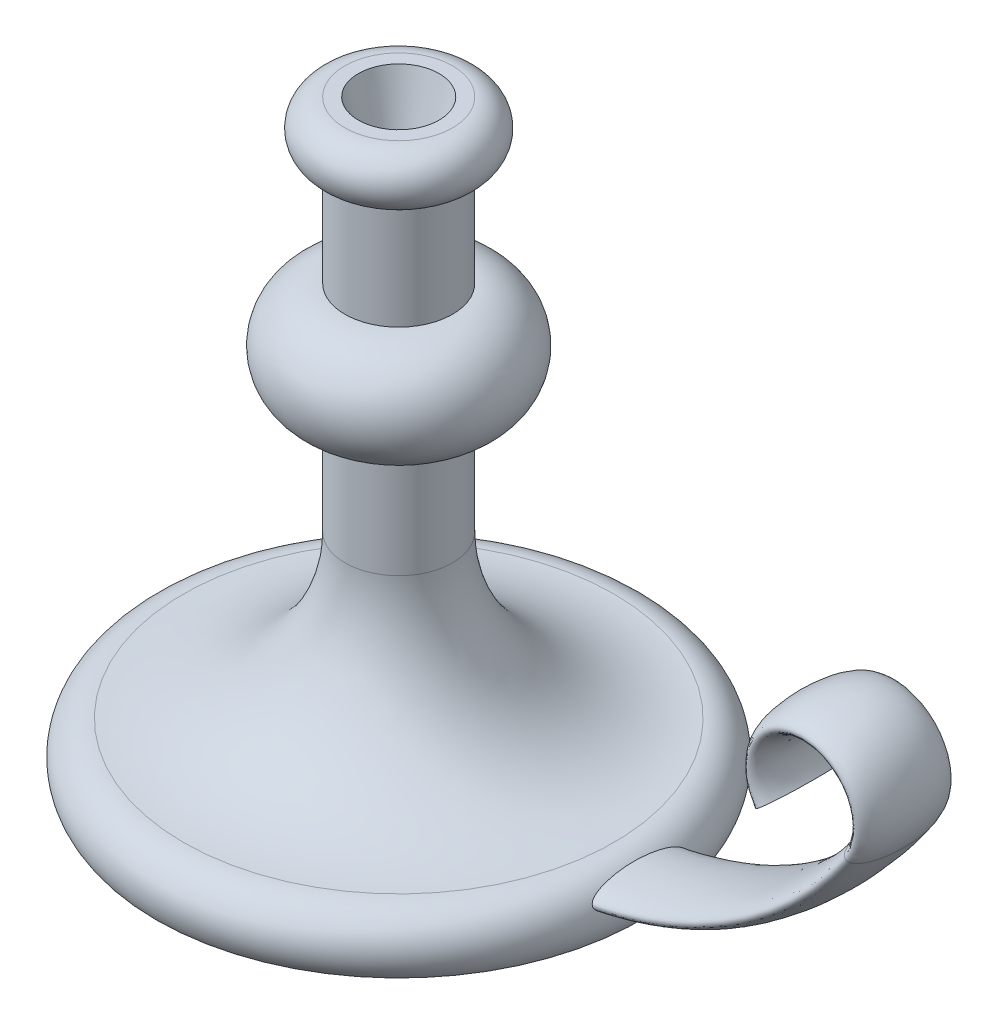
SolidWorks part; units mm, degrees
ref_plane "Front Plane" through (0, 0, 0) normal (0, 0, 1) x (1, 0, 0)
ref_plane "Top Plane" through (0, 0, 0) normal (0, 1, 0) x (1, 0, 0)
ref_plane "Right Plane" through (0, 0, 0) normal (1, 0, 0) x (0, 0, -1)
sketch "Sketch1" plane through (0, 0, 0) normal (0, 0, 1) x (1, 0, 0)
  line L0 (0, 0) -> (0, 220)
  line L1 (0, 220) -> (20, 220)
  line L2 (20, 200) -> (20, 160)
  line L3 (20, 120) -> (20, 80)
  line L4 (90, 0) -> (0, 0)
  arc A0 (20, 220) -> (20, 200) centre (20, 210) cw
  arc A1 (20, 160) -> (20, 120) centre (20, 140) cw
  arc A2 (20, 80) -> (80, 20) centre (80, 80) ccw
  arc A3 (80, 20) -> (90, 0) centre (80, 7.5) cw
  dimension "D3" = 10
  dimension "D5" = 20
  dimension "D6" = 60
  dimension "D7" = 12.5
  dimension "D1" = 220
  dimension "D2" = 20
  dimension "D4" = 40
  dimension "D8" = 80
  dimension "D9" = 90
revolve "Revolve1" add sketch "Sketch1" angle 360 about L0
sketch "Sketch2" plane through (0, 0, 0) normal (0, 0, 1) x (1, 0, 0)
  line L0 (0, 10) -> (60, 10)
  line L1 (-90, 0) -> (90, 0) construction
  arc A0 (60, 10) -> (183.5921, 75) centre (60, 160) ccw
  arc A1 (183.5921, 75) -> (150.6342, 75) centre (167.1131, 86.3333) ccw
  point P6 (0, 0)
  point P11 (60, 160)
  point P12 (150.4294, 75)
  point P13 (0, 0)
  dimension "D3" = 150
  dimension "D5" = 20
  dimension "D1" = 60
  dimension "D2" = 10
  dimension "D4" = 65
sketch "Sketch3" plane through (0, 0, 0) normal (1, 0, 0) x (0, 0, -1)
  ellipse E0 centre (0, 10) end of major axis (-17.5, 10) minor radius 5
  point P0 (-17.1219, 13.618)
  point P1 (0, 8.6618)
  point P7 (0, 10.7132)
  dimension "D1" = 35
  dimension "D2" = 10
  dimension "D3" = 10
sweep "Sweep1" add profiles "Sketch3" path "Sketch2"
sketch "Sketch4" plane through (0, 220, 0) normal (0, 1, 0) x (1, 0, 0)
  circle A0 centre (0, 0) radius 15
  dimension "D1" = 30
extrude "Cut-Extrude1" cut sketch "Sketch4" against normal blind 25 draft 15
